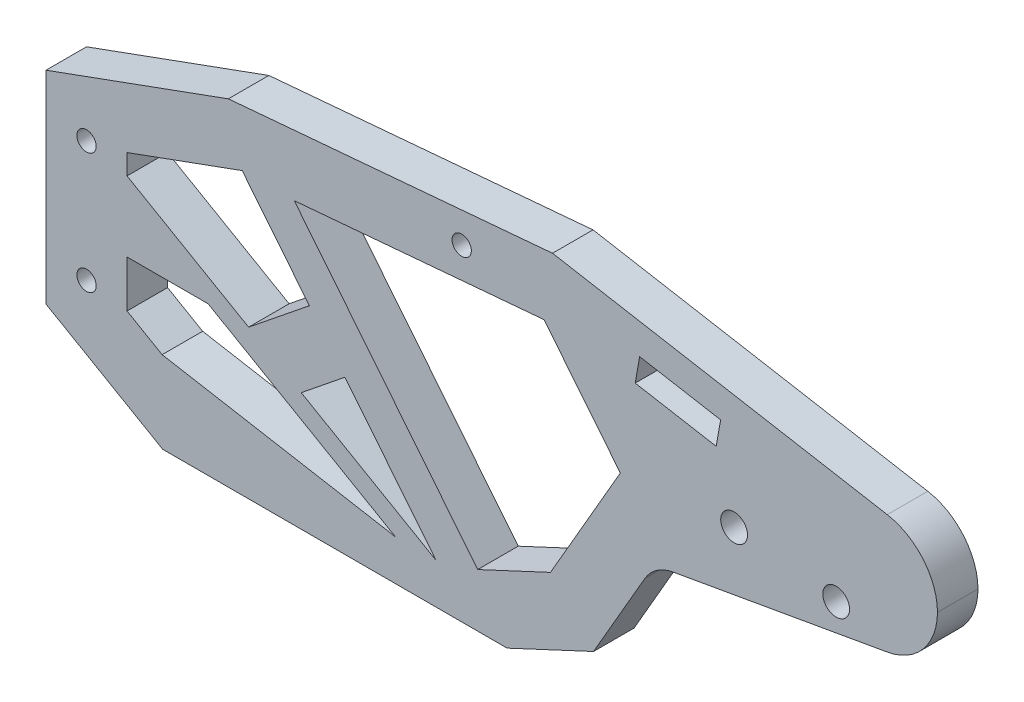
SolidWorks part; units mm, degrees
ref_plane "Plan de face" through (0, 0, 0) normal (0, 0, 1) x (1, 0, 0)
ref_plane "Plan de dessus" through (0, 0, 0) normal (0, 1, 0) x (1, 0, 0)
ref_plane "Plan de droite" through (0, 0, 0) normal (1, 0, 0) x (0, 0, -1)
sketch "Esquisse1" plane through (0, 0, 0) normal (0, 0, 1) x (1, 0, 0)
  line L1 (0, 0) -> (220, 0)
  line L2 (0, 0) -> (0, 90)
  line L3 (0, 90) -> (220, 90)
  line L4 (220, 0) -> (220, 90)
  dimension "D1" = 90
  dimension "D2" = 220
extrude "Boss.-Extru.1" add sketch "Esquisse1" along normal blind 10 contours L3 L4 L1 L2
sketch "Esquisse2" plane through (0, 0, 10) normal (0, 0, 1) x (1, 0, 0)
  line L0 (220, 73.2489) -> (125, 90)
  line L1 (220, 0) -> (220, 90) construction
  line L2 (0, 90) -> (220, 90) construction
  line L3 (125, 90) -> (45, 83.0009)
  line L4 (45, 83.0009) -> (0, 66.6222)
  line L5 (0, 0) -> (0, 90) construction
  line L6 (0, 66.6222) -> (0, 16.6222)
  line L7 (0, 16.6222) -> (28.7906, 0)
  line L8 (0, 0) -> (220, 0) construction
  line L9 (28.7906, 0) -> (113.7906, 0)
  line L10 (113.7906, 0) -> (135.1213, 9.9467)
  line L11 (135.1213, 9.9467) -> (150.1213, 35.9274)
  line L12 (150.1213, 35.9274) -> (220, 48.2489)
  line L13 (220, 48.2489) -> (220, 73.2489)
  dimension "D1" = 10
  dimension "D2" = 10
  dimension "D3" = 25
  dimension "D4" = 30
  dimension "D5" = 15
  dimension "D6" = 5
  dimension "D7" = 25
  dimension "D8" = 50
  dimension "D9" = 45
  dimension "D10" = 95
  dimension "D11" = 15
  dimension "D12" = 85
extrude "Enlèv. mat.-Extru.1" cut sketch "Esquisse2" against normal through all flip side to cut
sketch "Esquisse3" plane through (0, 0, 10) normal (0, 0, 1) x (1, 0, 0)
  line L0 (124.4956, 21.5425) -> (141.7327, 51.398)
  line L1 (141.7327, 51.398) -> (122.9121, 74.76)
  line L2 (122.9121, 74.76) -> (61.2631, 69.3664)
  line L3 (61.2631, 69.3664) -> (106.537, 13.1682)
  line L4 (96.248, 10) -> (73.7768, 37.8934)
  line L5 (73.7768, 37.8934) -> (62.9886, 29.2023)
  line L6 (62.9886, 29.2023) -> (96.248, 10)
  line L8 (20, 25.1543) -> (20, 36.7013)
  line L9 (20, 36.7013) -> (40, 36.7013)
  line L10 (40, 36.7013) -> (86.248, 10)
  line L11 (20, 54.0218) -> (49.9982, 36.7023)
  line L12 (49.9982, 36.7023) -> (65, 48.7879)
  line L13 (65, 48.7879) -> (48.4217, 69.3664)
  line L14 (48.4217, 69.3664) -> (20, 59.0218)
  line L15 (20, 59.0218) -> (20, 54.0218)
  line L16 (125, 90) -> (45, 83.0009) construction
  line L17 (135.1213, 9.9467) -> (150.1213, 35.9274) construction
  line L18 (0, 16.6222) -> (28.7906, 0) construction
  line L19 (113.7906, 0) -> (135.1213, 9.9467) construction
  line L20 (28.6603, 20.1543) -> (86.248, 10)
  line L21 (45, 83.0009) -> (0, 66.6222) construction
  line L22 (0, 16.6222) -> (0, 66.6222) construction
  line L23 (106.537, 13.1682) -> (124.4956, 21.5425)
  line L24 (28.7906, 0) -> (113.7906, 0) construction
  line L25 (20, 25.1543) -> (28.6603, 20.1543)
  dimension "D1" = 10
  dimension "D2" = 30
  dimension "D3" = 5
  dimension "D4" = 20
  dimension "D5" = 45
  dimension "D6" = 10
  dimension "D7" = 20
  dimension "D9" = 15
  dimension "D10" = 5
  dimension "D11" = 15
  dimension "D12" = 15
  dimension "D13" = 20
  dimension "D14" = 15
  dimension "D15" = 10
  dimension "D16" = 20
extrude "Enlèv. mat.-Extru.2" cut sketch "Esquisse3" against normal through all
fillet "Congé1" radius 15 2 edges at (220, 73.2489, 5) (220, 48.2489, 5)
sketch "Esquisse11" plane through (0, 0, 0) normal (0, 0, -1) x (-1, 0, 0)
  line L0 (-157.937, 55.9228) -> (-180.4672, 51.9502) construction
  point P2 (0, 0)
  point P3 (-157.937, 55.9228)
  dimension "D1" = 14.5326
  dimension "D2" = 1.413
  dimension "D3" = 1.132
  dimension "D4" = 37.0627
sketch "Esquisse4" plane through (0, 0, 10) normal (0, 0, 1) x (1, 0, 0)
  line L0 (194.9998, 50.5372) -> (194.9998, 77.6572) construction
  line L1 (207.6047, 75.4346) -> (125, 90) construction
  line L2 (169.8139, 53.8286) -> (194.9998, 50.5372) construction
  line L3 (157.937, 55.9228) -> (180.4672, 51.9502) construction
  circle A0 centre (194.9998, 50.5372) radius 3.305
  circle A1 centre (169.8139, 53.8286) radius 3.305
  point P8 (170.7798, 58.5896)
  point P10 (169.853, 54.1153)
  point P11 (0, 0)
  dimension "D1" = 6.61
  dimension "D2" = 25
  dimension "D4" = 25.4
  dimension "D3" = 27.12
extrude "Enlèv. mat.-Extru.3" cut sketch "Esquisse4" against normal through all
hole_wizard "Perçage pour écrous auto-bloquants 300® #6 (SP)1" positions "Esquisse5" profile "Esquisse6" hole size "#6-32" standard "PEM® Inch" end condition through all
sketch "Esquisse5" plane through (0, 0, 10) normal (0, 0, 1) x (1, 0, 0)
  line L21 (102.9121, 73.0103) -> (102.5846, 80.5103) construction
  line L22 (102.5846, 80.5103) -> (102.2572, 88.0103) construction
  line L24 (122.9121, 74.76) -> (61.2631, 69.3664) construction
  line L25 (125, 90) -> (45, 83.0009) construction
  point P41 (102.5846, 80.5103)
  dimension "D1" = 7.5
  dimension "D2" = 20
sketch "Esquisse6" plane through (102.5846, 80.5103, 10) normal (1, 0, 0) x (0, -1, 0)
  line L0 (0, 0) -> (0, 10)
  line L1 (0, 10) -> (2.3812, 10)
  line L2 (2.3812, 10) -> (2.3812, 0)
  line L5 (2.3812, 0) -> (0, 0)
  line L11 (0, -6.35) -> (0, 107.95) construction
  dimension "Diamètre du perçage jusqu'au prochain" = 4.7625
  dimension "Profondeur du perçage jusqu'au prochain" = 10
hole_wizard "Perçage pour écrous auto-bloquants 300® #6 (SP)2" positions "Esquisse8" profile "Esquisse9" hole size "#6-32" standard "PEM® Inch" end condition through all
sketch "Esquisse8" plane through (0, 0, 10) normal (0, 0, 1) x (1, 0, 0)
  line L0 (10, 56.5218) -> (0, 56.5218) construction
  line L1 (0, 16.6222) -> (0, 66.6222) construction
  line L3 (10, 56.5218) -> (20, 56.5218) construction
  line L4 (20, 59.0218) -> (20, 54.0218) construction
  line L6 (10, 56.5218) -> (10, 26.7227) construction
  point P0 (10, 56.5218)
  point P2 (10, 26.7227)
  point P23 (0, 41.6222)
  point P24 (10, 41.6222)
  point P26 (20, 56.5218)
sketch "Esquisse9" plane through (10, 56.5218, 10) normal (1, 0, 0) x (0, -1, 0)
  line L0 (0, 0) -> (0, 10)
  line L1 (0, 10) -> (2.3812, 10)
  line L2 (2.3812, 10) -> (2.3812, 0)
  line L5 (2.3812, 0) -> (0, 0)
  line L11 (0, -6.35) -> (0, 107.95) construction
  dimension "Diamètre du perçage jusqu'au prochain" = 4.7625
  dimension "Profondeur du perçage jusqu'au prochain" = 10
sketch "Esquisse10" plane through (0, 0, 10) normal (0, 0, 1) x (1, 0, 0)
  line L0 (146.4982, 78.6545) -> (145.4042, 72.4502)
  line L1 (146.4982, 78.6545) -> (166.4898, 75.1294)
  line L2 (145.4042, 72.4502) -> (165.3958, 68.9252)
  line L3 (166.4898, 75.1294) -> (165.3958, 68.9252)
  line L4 (155.4, 70.6877) -> (194.9998, 50.5372) construction
  line L6 (207.6047, 75.4346) -> (125, 90) construction
  dimension "D1" = 20.3
  dimension "D2" = 6.3
  dimension "D3" = 44.4318
  dimension "D4" = 7.44
extrude "Enlèv. mat.-Extru.4" cut sketch "Esquisse10" against normal blind 10 contours L1 L3 L2 L0
fillet "Congé2" radius 10 1 edges at (150.1213, 35.9274, 5)
